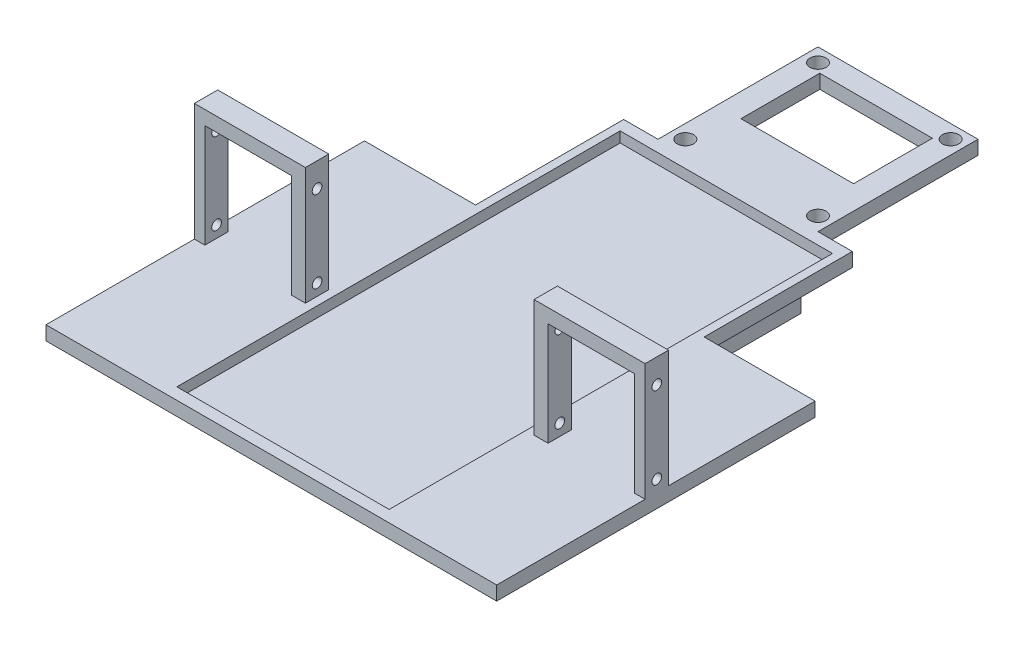
SolidWorks part; units mm, degrees
ref_plane "Front Plane" through (0, 0, 0) normal (0, 0, 1) x (1, 0, 0)
ref_plane "Top Plane" through (0, 0, 0) normal (0, 1, 0) x (1, 0, 0)
ref_plane "Right Plane" through (0, 0, 0) normal (1, 0, 0) x (0, 0, -1)
sketch "Sketch1" plane through (0, 0, 0) normal (0, 0, 1) x (1, 0, 0)
  line L1 (-48.292, 0) -> (48.292, 0)
  line L2 (-48.292, 0) -> (-48.292, 3)
  line L3 (-48.292, 3) -> (48.292, 3)
  line L4 (48.292, 0) -> (48.292, 3)
  point P4 (0, 0)
  dimension "D1" = 3
  dimension "D2" = 96.584
extrude "Boss-Extrude1" add sketch "Sketch1" along normal blind 100
sketch "Sketch7" plane through (0, 3, 0) normal (0, 1, 0) x (1, 0, 0)
  line L0 (-48.292, -100) -> (-48.292, 0) construction
  line L1 (22.75, -2.5) -> (-22.75, -2.5)
  line L2 (22.75, -2.5) -> (22.75, -97.5)
  line L3 (22.75, -97.5) -> (-22.75, -97.5)
  line L4 (-22.75, -2.5) -> (-22.75, -97.5)
  line L5 (22.75, -2.5) -> (-22.75, -97.5) construction
  line L6 (22.75, -97.5) -> (-22.75, -2.5) construction
  point P0 (0, -50)
  point P10 (-48.292, -50)
  dimension "D1" = 95
  dimension "D2" = 45.5
extrude "Cut-Extrude2" cut sketch "Sketch7" against normal blind 2.25
sketch "Sketch2" plane through (0, 0, 100) normal (0, 0, 1) x (1, 0, 0)
  line L0 (48.292, 3) -> (-48.292, 3) construction
  line L1 (-24.5, 3) -> (-27.5, 3)
  line L2 (-24.5, 3) -> (-24.5, 28.1806)
  line L3 (-24.5, 28.1806) -> (-27.5, 28.1805)
  line L4 (-27.5, 3) -> (-27.5, 28.1805)
  line L6 (-24.5, 28.1806) -> (-48.292, 28.1805)
  line L7 (-24.5, 28.1806) -> (-24.5, 25.1806)
  line L8 (-24.5, 25.1806) -> (-48.292, 25.1805)
  line L9 (-48.292, 28.1805) -> (-48.292, 25.1805)
  line L10 (-48.292, 28.1805) -> (-46.042, 28.1805)
  line L11 (-48.292, 28.1805) -> (-48.292, 3)
  line L12 (-48.292, 3) -> (-46.042, 3)
  line L13 (-46.042, 28.1805) -> (-46.042, 3)
  line M11 (48.292, 3) -> (-48.292, 3)
  dimension "D1" = 27.5
  dimension "D2" = 3
  dimension "D3" = 3
  dimension "D4" = 2.25
  dimension "D5" = 18.542
  dimension "D6" = 22.1806
extrude "Boss-Extrude2" add sketch "Sketch2" against normal blind 5 from offset 31.8 contours L2 L8 L4 M11 | L8 L2 L3 L4 | L6 L13 L8 L4 | L13 L6 L9 L8 | L13 L8 L11 L12 M11 region at (-26, 14.0903, 100) region at (-26, 26.6806, 100) region at (-36.771, 26.6805, 100) region at (-47.167, 14.0903, 100) region at (-47.167, 26.6805, 100) offset against normal yes
mirror "Mirror1" about plane through (0, 0, 0) normal (1, 0, 0) of "Boss-Extrude2"
sketch "Sketch4" plane through (48.292, 0, 0) normal (1, 0, 0) x (0, 0, -1)
  line L0 (-63.2, 28.1805) -> (-68.2, 28.1805) construction
  line L2 (-100, 0) -> (0, 0) construction
  circle A0 centre (-65.7, 5.5) radius 1.0375
  circle A1 centre (-65.7, 23) radius 1.0375
  point P5 (-65.7, 28.1806)
  dimension "D1" = 2.075
  dimension "D3" = 2.075
  dimension "D2" = 5.5
  dimension "D4" = 17.5
extrude "Cut-Extrude1" cut sketch "Sketch4" against normal through all
sketch "Sketch8" plane through (0, 3, 0) normal (0, 1, 0) x (1, 0, 0)
  line L0 (-22.75, -2.5) -> (-22.75, -97.5) construction
  line L1 (-48.292, 0) -> (-24.5, 0)
  line L2 (-48.292, 0) -> (-48.292, -31.75)
  line L3 (-48.292, -31.75) -> (-24.5, -31.75)
  line L4 (-24.5, 0) -> (-24.5, -31.75)
  line L6 (0, -6.9919) -> (0, -47.353) construction
  line L7 (48.292, -100) -> (-48.292, -100) construction
  line L8 (48.292, 0) -> (48.292, -31.75)
  line L9 (48.292, -31.75) -> (24.5, -31.75)
  line L10 (24.5, 0) -> (24.5, -31.75)
  line L11 (48.292, 0) -> (24.5, 0)
  dimension "D1" = 1.75
  dimension "D2" = 68.25
extrude "Cut-Extrude3" cut sketch "Sketch8" against normal through all
sketch "Sketch9" plane through (0, 3, 0) normal (0, 1, 0) x (1, 0, 0)
  line L1 (-17.145, 0) -> (17.145, 0)
  line L2 (-17.145, 0) -> (-17.145, 34.29)
  line L3 (-17.145, 34.29) -> (17.145, 34.29)
  line L4 (17.145, 0) -> (17.145, 34.29)
  line L5 (24.5, 0) -> (-24.5, 0) construction
  point P4 (0, 34.29)
  dimension "D1" = 34.29
  dimension "D2" = 34.29
extrude "Boss-Extrude4" add sketch "Sketch9" against normal blind 3
sketch "Sketch10" plane through (0, 3, 0) normal (0, 1, 0) x (1, 0, 0)
  line L0 (-17.145, 34.29) -> (-17.145, 0) construction
  line L1 (17.145, 34.29) -> (-17.145, 34.29) construction
  line L2 (0, 36.6553) -> (0, -5.2305) construction
  line L3 (-21.3442, 17.145) -> (25.5089, 17.145) construction
  line L5 (-12.065, 12.7052) -> (12.065, 12.7052)
  line L6 (-12.065, 12.7052) -> (-12.065, 29.5962)
  line L7 (-12.065, 29.5962) -> (12.065, 29.5962)
  line L8 (12.065, 12.7052) -> (12.065, 29.5962)
  circle A0 centre (-14.2113, 31.3563) radius 1.7399
  circle A1 centre (14.2113, 31.3563) radius 1.7399
  circle A2 centre (14.2113, 2.9337) radius 1.7399
  circle A3 centre (-14.2113, 2.9337) radius 1.7399
  point P21 (0, 29.5962)
  dimension "D3" = 3.4798
  dimension "D1" = 2.9337
  dimension "D2" = 2.9337
  dimension "D4" = 17.145
  dimension "D5" = 16.891
  dimension "D6" = 24.13
  dimension "D7" = 4.6938
extrude "Cut-Extrude4" cut sketch "Sketch10" against normal through all
sketch "Sketch11" plane through (0, 0, 0) normal (0, -1, 0) x (1, 0, 0)
  line L1 (-17.5, 4) -> (17.5, 4)
  line L2 (-17.5, 4) -> (-17.5, 24)
  line L3 (-17.5, 24) -> (17.5, 24)
  line L4 (17.5, 4) -> (17.5, 24)
  point P4 (0, 4)
  dimension "D1" = 20
  dimension "D2" = 35
  dimension "D3" = 4
extrude "Boss-Extrude5" add sketch "Sketch11" along normal blind 10
sketch "Sketch12" plane through (0, -10, 0) normal (0, -1, 0) x (1, 0, 0)
  line L0 (-17.5, 24) -> (-17.5, 4) construction
  circle A0 centre (0, 14) radius 6.25
  circle A1 centre (0, 14) radius 8.5
  point P2 (0, 0)
  point P4 (0, 0)
  point P7 (-17.5, 14)
  dimension "D1" = 12.5
  dimension "D2" = 2.25
extrude "Boss-Extrude6" add sketch "Sketch12" along normal blind 13.85
ref_plane "Plane1" through (0, -16.35, 0) normal (0, -1, 0) x (-1, 0, 0)
sketch "Sketch13" plane through (0, -16.35, 0) normal (0, -1, 0) x (-1, 0, 0)
  line L0 (0, -6.85) -> (0, -21.15)
  circle A2 centre (0, -14) radius 7.15
  arc A3 (0, -21.15) -> (0, -6.85) centre (0, -14) ccw
  dimension "D1" = 0.9
revolve "Cut-Revolve1" cut sketch "Sketch13" angle 360 about L0 region at (-3.0346, -16.35, 14)
sketch "Sketch14" plane through (0, 0, 4) normal (0, 0, -1) x (-1, 0, 0)
  line L1 (-12.9462, -32.7555) -> (12.6056, -32.7555)
  line L2 (-12.9462, -32.7555) -> (-12.9462, -19.6957)
  line L3 (-12.9462, -19.6957) -> (12.6056, -19.6957)
  line L4 (12.6056, -32.7555) -> (12.6056, -19.6957)
extrude "Cut-Extrude5" cut sketch "Sketch14" against normal through all
sketch "Sketch15" plane through (0, -19.6957, 0) normal (0, -1, 0) x (1, 0, 0)
  line L0 (17.5, 24) -> (-17.5, 24) construction
  line L1 (2.125, 4) -> (-2.125, 4)
  line L2 (2.125, 4) -> (2.125, 24)
  line L3 (2.125, 24) -> (-2.125, 24)
  line L4 (-2.125, 4) -> (-2.125, 24)
  line L5 (2.125, 4) -> (-2.125, 24) construction
  line L6 (2.125, 24) -> (-2.125, 4) construction
  line L8 (-10.6247, 11.875) -> (10.6247, 11.875)
  line L9 (-10.6247, 11.875) -> (-10.6247, 16.125)
  line L10 (-10.6247, 16.125) -> (10.6247, 16.125)
  line L11 (10.6247, 11.875) -> (10.6247, 16.125)
  line L12 (-10.6247, 11.875) -> (10.6247, 16.125) construction
  line L13 (-10.6247, 16.125) -> (10.6247, 11.875) construction
  point P0 (0, 14)
  point P8 (0, 14)
  circle M3 centre (0, 14) radius 6.3189
  circle M4 centre (0, 14) radius 8.5
  dimension "D1" = 4.25
  dimension "D2" = 4.25
extrude "Cut-Extrude6" cut sketch "Sketch15" against normal up to surface (9.6957 mm away) contours L4 L2 L3 M4 | L4 L2 M3 M4 | L4 L10 L2 M3 | L10 L8 M3 M4 | L8 L11 L10 M4 | L10 L2 L8 M3 | L10 L4 L8 L2 | L10 L8 L4 M3 | L10 L9 L8 M4 | L10 L8 M4 M3 | L4 L2 M4 M3 | L8 L4 L2 M3 | L4 L1 L2 M4 region at (0, -19.6957, 4.7967) region at (0, -19.6957, 6.6971) region at (0, -19.6957, 9.8372) region at (9.5162, -19.6957, 14) region at (7.3029, -19.6957, 14) region at (-7.3029, -19.6957, 14) region at (-9.5162, -19.6957, 14) region at (0, -19.6957, 14) region at (4.1628, -19.6957, 14) region at (-4.1628, -19.6957, 14) region at (0, -19.6957, 18.1628) region at (0, -19.6957, 21.3029) region at (0, -19.6957, 23.2033) up to face at (0, -10, 22.5)
